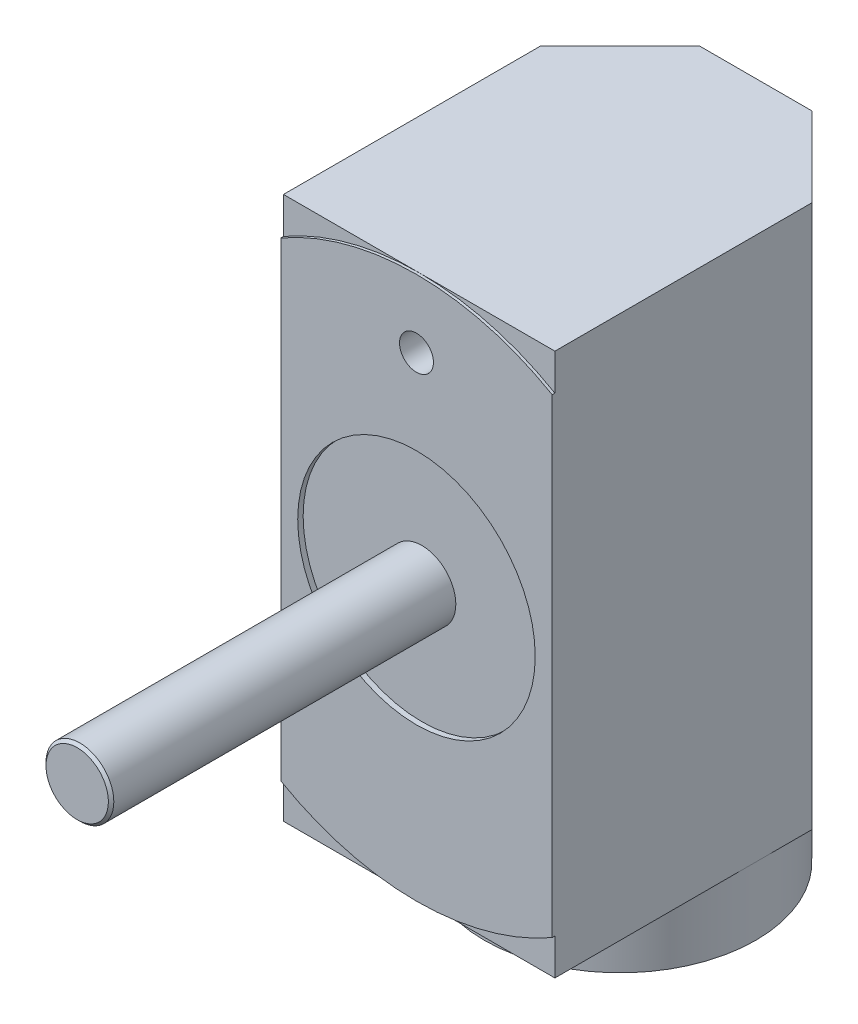
SolidWorks part; units mm, degrees
note: The reader was unsure of these and kept them because the rebuilt part matched: shared geometry of "Sketch5<4>", "Sketch4<4>".
ref_plane "Front Plane" through (0, 0, 0) normal (0, 0, 1) x (1, 0, 0)
ref_plane "Top Plane" through (0, 0, 0) normal (0, 1, 0) x (1, 0, 0)
ref_plane "Right Plane" through (0, 0, 0) normal (1, 0, 0) x (0, 0, -1)
sketch "Sketch1" plane through (0, 0, 0) normal (0, 1, 0) x (1, 0, 0)
  line L0 (-29.3926, 0) -> (34.6929, 0) construction
  line L1 (0, 32.3318) -> (0, -33.0064) construction
  line L2 (6.35, -9.525) -> (-6.35, -9.525)
  line L3 (-6.35, -9.525) -> (-6.35, 2.6303)
  line L4 (-6.35, 2.6303) -> (-2.6303, 6.35)
  line L5 (-2.6303, 6.35) -> (2.6303, 6.35)
  line L6 (6.35, 2.6303) -> (2.6303, 6.35)
  line L7 (6.35, -9.525) -> (6.35, 2.6303)
  point P10 (0, 6.35)
  point P13 (0, -9.525)
  dimension "D1" = 9.525
  dimension "D2" = 15.875
  dimension "D3" = 6.35
  dimension "D4" = 45
extrude "Boss-Extrude2" add sketch "Sketch1" against normal blind 25.4
sketch "Sketch2" plane through (0, -25.4, 0) normal (0, -1, 0) x (1, 0, 0)
  circle A0 centre (0, 0) radius 6.35
  dimension "D1" = 12.7
extrude "Boss-Extrude3" add sketch "Sketch2" along normal blind 3.175
sketch "Sketch3" plane through (0, -28.575, 0) normal (0, -1, 0) x (1, 0, 0)
  circle A0 centre (0, 0) radius 4.7625
  dimension "D1" = 9.525
extrude "Cut-Extrude1" cut sketch "Sketch3" against normal blind 26.1937
sketch "Sketch4" plane through (0, 0, 9.525) normal (0, 0, 1) x (1, 0, 0)
  line L0 (-6.35, -28.575) -> (6.35, -28.575) construction
  circle A0 centre (0, -12.7) radius 1.5875
  circle A1 centre (0, -3.175) radius 0.7938
  dimension "D1" = 3.175
  dimension "D2" = 1.5875
  dimension "D3" = 15.875
  dimension "D4" = 9.525
extrude "Boss-Extrude4" add sketch "Sketch4" along normal blind 15.875 contours A0
sketch "Sketch5" plane through (0, 0, 9.525) normal (0, 0, 1) x (1, 0, 0)
  line L0 (6.35, -1.7015) -> (6.35, 0)
  line L1 (6.35, -25.4) -> (6.35, 0) construction
  line L2 (6.35, 0) -> (-6.35, 0)
  line L3 (-6.35, 0) -> (-6.35, -1.7015)
  line L6 (-6.35, -25.4) -> (-6.35, -23.6985)
  line L7 (6.35, -23.6985) -> (6.35, -25.4)
  line L8 (6.35, -25.4) -> (-6.35, -25.4)
  circle A0 centre (0, -12.7) radius 5.5562
  arc A1 (-6.35, -23.6985) -> (6.35, -23.6985) centre (0, -12.7) ccw
  arc A2 (6.35, -1.7015) -> (-6.35, -1.7015) centre (0, -12.7) ccw
  circle M7 centre (0, -12.7) radius 1.5875
  line M8 (6.35, 0) -> (-6.35, 0)
  line M9 (-6.35, 0) -> (-6.35, -25.4)
  line M10 (-6.35, -25.4) -> (6.35, -25.4)
  line M11 (6.35, -25.4) -> (6.35, 0)
  dimension "D1" = 11.1125
extrude "Cut-Extrude2" cut sketch "Sketch5" against normal blind 0.254 contours A0 M7 | L8 L6 A1 L7 | L2 L3 A2 L0
extrude "Cut-Extrude4" cut sketch "Sketch5<4>" against normal blind 0.127 contours A2 M11 M8 | A2 L2 M9 | A1 M9 M10 | A1 L8 M11
sketch "Sketch5<4>" plane through (0, 0, 9.525) normal (0, 0, 1) x (1, 0, 0) same geometry as "Sketch5"
extrude "Cut-Extrude6" cut sketch "Sketch4<4>" against normal blind 5.588 contours A1
sketch "Sketch4<4>" plane through (0, 0, 9.525) normal (0, 0, 1) x (1, 0, 0) same geometry as "Sketch4"
chamfer "Chamfer1" distance 0.127 angle 45 1 edges at (1.5875, -12.7, 25.4)
